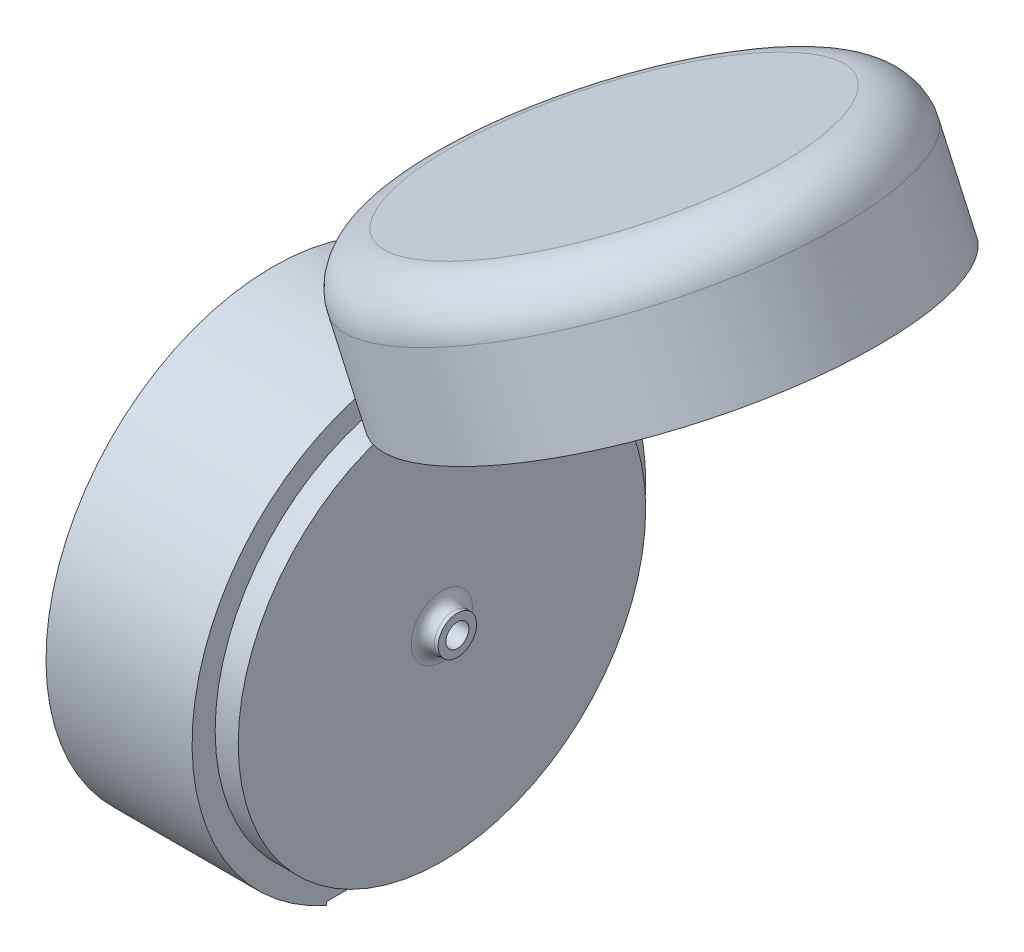
SolidWorks part; units mm, degrees
material "PP Homopolymer"
ref_plane "Front Plane" through (0, 0, 0) normal (0, 0, 1) x (1, 0, 0)
ref_plane "Top Plane" through (0, 0, 0) normal (0, 1, 0) x (1, 0, 0)
ref_plane "Right Plane" through (0, 0, 0) normal (1, 0, 0) x (0, 0, -1)
sketch "Bottom Sketch" plane through (0, 0, 0) normal (1, 0, 0) x (0, 0, -1)
  circle A0 centre (0, 0) radius 0.75
  circle A1 centre (0, 0) radius 11.75
  circle A2 centre (0, 0) radius 14.75
  circle A3 centre (0, 0) radius 13.25
  dimension "D1" = 1.5
  dimension "D2" = 3
  dimension "D3" = 29.5
  dimension "D4" = 1.5
extrude "Bottom Base Extrude" add sketch "Bottom Sketch" along normal blind 9.5 separate body contours A2
extrude "Raised Platform Extrude" add sketch "Sketch5<9>" along normal blind 1.5 from surface contours A3 A1 | A1 A0 region at (0, 0, 11.4177) region at (0, 0, 12.8752) starting at face at (9.5, 0, -14.75)
sketch "Sketch5<9>" plane through (0, 0, 0) normal (1, 0, 0) x (0, 0, -1) same geometry as "Bottom Sketch"
extrude "Hollow Base Extruded Cut" cut sketch "Sketch5<10>" along normal blind 8 contours A1 A0 | A0 region at (0, 0, 11.4177)
sketch "Sketch5<10>" plane through (0, 0, 0) normal (1, 0, 0) x (0, 0, -1) same geometry as "Bottom Sketch"
extrude "Nozzle Extruded Cut" cut sketch "Sketch5<11>" along normal through all and the other way through all contours A0
sketch "Sketch5<11>" plane through (0, 0, 0) normal (1, 0, 0) x (0, 0, -1) same geometry as "Bottom Sketch"
sketch "Hinge Sketch" plane through (0, 0, 0) normal (0, 0, 1) x (1, 0, 0)
  line L0 (9.5, -13.25) -> (9.5, 13.25) construction
  line L2 (9.5, 18.3032) -> (12.2695, 19.5946)
  line L3 (12.2695, 19.5946) -> (12.9029, 18.235)
  line L4 (12.9029, 18.235) -> (10.1836, 16.968)
  line L5 (0, -14.75) -> (0, 14.75) construction
  line L6 (0, -14.75) -> (0, 14.75) construction
  line L9 (9.5, -13.25) -> (9.5, 13.25) construction
  line L11 (0, 0) -> (17.8515, 0) construction
  line L12 (9.5, 13.25) -> (9.5, 16.25)
  line L13 (9.5, 14.75) -> (0, 14.75) construction
  line L14 (9.5, 14.75) -> (8, 14.75)
  line L15 (9.5, 18.3032) -> (10.1836, 16.968) construction
  arc A0 (8, 14.75) -> (9.5, 18.3032) centre (10.8672, 15.6328) cw
  arc A1 (10.1836, 16.968) -> (9.5, 16.25) centre (10.8672, 15.6328) ccw
  point P4 (0, 0)
  dimension "D1" = 3
  dimension "D3" = 1.5
  dimension "D6" = 1.5
  dimension "D2" = 3
  dimension "D4" = 115
  dimension "D5" = 3
  dimension "D7" = 1.5
revolve "Hinge Revolve" add sketch "Hinge Sketch" angle 22 mid plane about L11 region at (9.9859, 17.2505, 0)
ref_plane "Lid Plane" through (-4.5383, 9.9234, 0) normal (-0.4159, 0.9094, 0) x (-0.9065, -0.4146, 0.0806)
sketch "Lid Sketch" plane through (-4.5383, 9.9234, 0) normal (-0.4159, 0.9094, 0) x (-0.9065, -0.4146, 0.0806)
  line L1 (-19.2552, 1.5567) -> (-16.265, 1.3149) construction
  line L2 (-33.4035, 2.7005) -> (-16.0859, 1.3004) construction
  circle A0 centre (-33.4035, 2.7005) radius 14.75
  circle A1 centre (-33.4035, 2.7005) radius 13.25
  circle A2 centre (-33.4035, 2.7005) radius 11.75
  dimension "D1" = 29.5
  dimension "D2" = 1.5
  dimension "D3" = 1.5
extrude "Lid Extrude" add sketch "Lid Sketch" along normal blind 9 contours A0 A1 | A1 region at (38.9302, 29.8031, -1.1549)
extrude "Lid Lip Extruded Cut" cut sketch "Lid Sketch<4>" along normal blind 1.5 contours A2 A1 region at (37.6089, 29.1988, -1.0375)
sketch "Lid Sketch<4>" plane through (-4.5383, 9.9234, 0) normal (-0.4159, 0.9094, 0) x (-0.9065, -0.4146, 0.0806) same geometry as "Lid Sketch"
extrude "Lid Inner Extruded Cut" cut sketch "Lid Sketch<5>" along normal blind 6 contours A2 region at (25.9382, 23.8614, 0)
sketch "Lid Sketch<5>" plane through (-4.5383, 9.9234, 0) normal (-0.4159, 0.9094, 0) x (-0.9065, -0.4146, 0.0806) same geometry as "Lid Sketch"
fillet "Lid Fillet" radius 3 2 edges at (12.7572, 24.431, 0) (8.7813, 25.9115, 0)
ref_plane "Opener Slot Plane" through (0, -14.75, 0) normal (0, -1, 0) x (-1, 0, 0)
sketch "Opener Slot Sketch" plane through (0, -14.75, 0) normal (0, -1, 0) x (-1, 0, 0)
  line L0 (-9.5, 14.75) -> (-9.5, -14.75) construction
  line L1 (-9.5, 5.9934) -> (-9.5, -5.9934)
  line L2 (-9.5, -5.9934) -> (-4.246, -3.6542)
  line L3 (-9.5, 5.9934) -> (-4.246, 3.6542)
  line L4 (-2, 1) -> (-2, -1)
  line L6 (-9.7953, 0) -> (2.1617, 0) construction
  arc A0 (-4.246, -3.6542) -> (-2, 1) centre (-5.873, 0) ccw
  arc A1 (-4.246, 3.6542) -> (-2, -1) centre (-5.873, 0) cw
  point P6 (-2, 0)
  dimension "D3" = 4
  dimension "D1" = 7.5
  dimension "D2" = 2
  dimension "D4" = 48
extrude "Opener Slot Extruded Cut" cut sketch "Opener Slot Sketch" against normal blind 1.5 contours L1 L6 L4 A1 L3 | L6 L1 L2 A0 L4 region at (6.3426, -14.75, -2.2643) region at (6.3426, -14.75, 2.2643)
sketch "Sketch5" plane through (0, 0, 0) normal (1, 0, 0) x (0, 0, -1)
  circle A0 centre (0, 0) radius 0.75 construction
  circle A1 centre (0, 0) radius 0.75
  circle A2 centre (0, 0) radius 1.25
  dimension "D1" = 2.5
extrude "Nozzle Extrude" add sketch "Sketch5" along normal blind 1 from surface starting at face at (11, 0, -13.25)
fillet "Inner Nozzle Fillet" radius 1.25 1 edges at (8, 0, -0.75)
fillet "Outer Nozzle Fillet" radius 0.75 1 edges at (11, 0, -1.25)
sketch "Sketch6" plane through (-4.5383, 9.9234, 0) normal (-0.4159, 0.9094, 0) x (-0.9065, -0.4146, 0.0806)
  circle A0 centre (-33.4035, 2.7005) radius 11.75 construction
  circle A1 centre (-33.4035, 2.7005) radius 11.75 construction
  circle A2 centre (-33.4035, 2.7005) radius 0.75
  dimension "D1" = 1.5
extrude "Tip Extrude" add sketch "Sketch6" against normal blind 5 from surface starting at face at (15.4854, 25.6787, 0)
fillet "Tip Fillet" radius 2.5 1 edges at (22.7607, 29.0059, 0)
